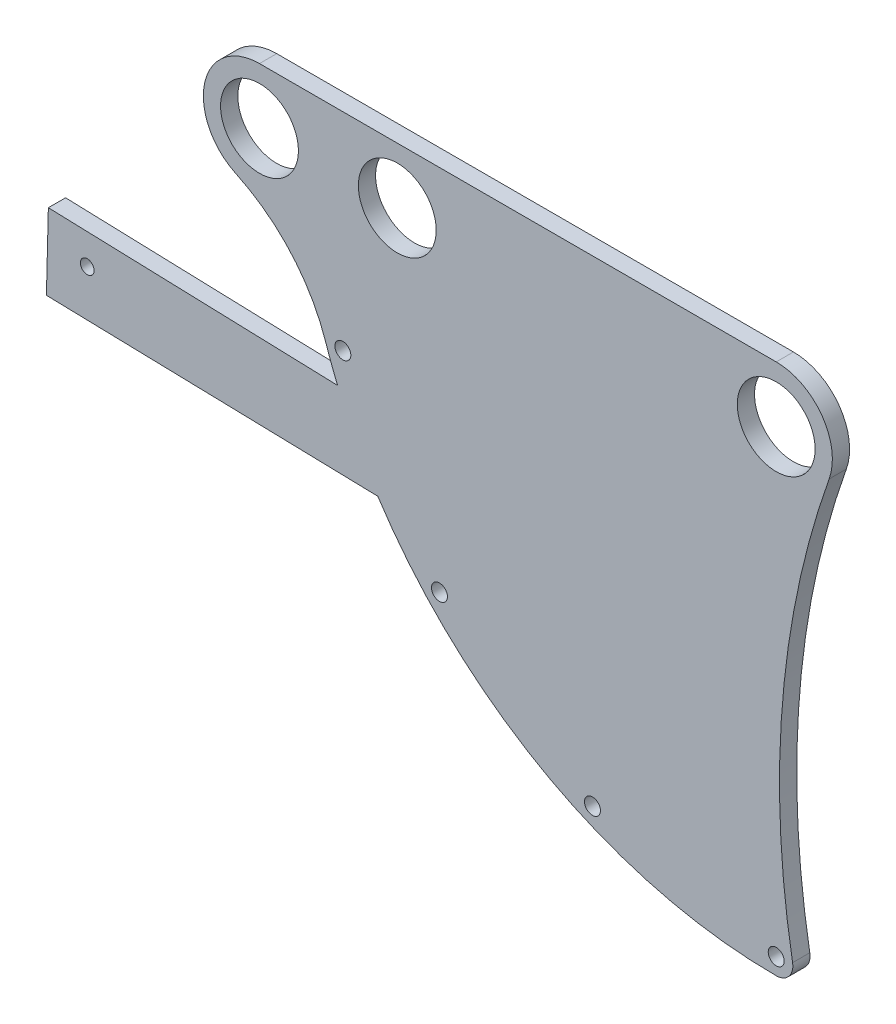
SolidWorks part; units mm, degrees
material "6061-T6 (SS)"
ref_plane "Front Plane" through (0, 0, 0) normal (0, 0, 1) x (1, 0, 0)
ref_plane "Top Plane" through (0, 0, 0) normal (0, 1, 0) x (1, 0, 0)
ref_plane "Right Plane" through (0, 0, 0) normal (1, 0, 0) x (0, 0, -1)
sketch "Sketch1" plane through (0, 0, 0) normal (0, 0, 1) x (1, 0, 0)
  line L1 (0, 0) -> (422.275, 0) construction
  line L2 (0, 0) -> (0, 250.825) construction
  line L3 (0, 250.825) -> (422.275, 250.825) construction
  line L4 (422.275, 0) -> (422.275, 250.825) construction
  line L5 (129.8504, 75.2912) -> (186.2558, 35.1899) construction
  line L6 (186.2558, 35.1899) -> (254, 21.033) construction
  line L7 (342.9, 250.825) -> (342.9, 0) construction
  line L8 (382.5875, 27.383) -> (382.5875, 190.197) construction
  line L10 (422.275, 27.383) -> (382.5875, 27.383) construction
  line L11 (0, 225.425) -> (0, 0)
  line L13 (254, 21.033) -> (129.8504, 75.2912) construction
  line L14 (250.3338, 27.383) -> (246.6677, 21.033) construction
  line L15 (246.6677, 21.033) -> (250.3338, 14.683) construction
  line L16 (250.3338, 14.683) -> (257.6662, 14.683) construction
  line L17 (257.6662, 14.683) -> (261.3323, 21.033) construction
  line L18 (261.3323, 21.033) -> (257.6662, 27.383) construction
  line L19 (257.6662, 27.383) -> (250.3338, 27.383) construction
  line L20 (185.4394, 42.4767) -> (179.5371, 38.1263) construction
  line L21 (179.5371, 38.1263) -> (180.3535, 30.8395) construction
  line L22 (180.3535, 30.8395) -> (187.0723, 27.9032) construction
  line L23 (187.0723, 27.9032) -> (192.9746, 32.2536) construction
  line L24 (192.9746, 32.2536) -> (192.1582, 39.5404) construction
  line L25 (192.1582, 39.5404) -> (185.4394, 42.4767) construction
  line L26 (132.0204, 82.2951) -> (124.8698, 80.6725) construction
  line L27 (124.8698, 80.6725) -> (122.6998, 73.6686) construction
  line L28 (122.6998, 73.6686) -> (127.6804, 68.2874) construction
  line L29 (127.6804, 68.2874) -> (134.8309, 69.91) construction
  line L30 (134.8309, 69.91) -> (137.0009, 76.9139) construction
  line L31 (137.0009, 76.9139) -> (132.0204, 82.2951) construction
  line L32 (91.186, 186.5308) -> (91.186, 193.8632) construction
  line L33 (91.186, 193.8632) -> (84.836, 197.5293) construction
  line L34 (84.836, 197.5293) -> (78.486, 193.8632) construction
  line L35 (78.486, 193.8632) -> (78.486, 186.5308) construction
  line L36 (78.486, 186.5308) -> (84.836, 182.8647) construction
  line L37 (84.836, 182.8647) -> (91.186, 186.5308) construction
  line L38 (186.2558, 35.1899) -> (94.2245, 134.6249) construction
  line L39 (186.2558, 35.1899) -> (191.9252, 48.1621) construction
  line L40 (129.8504, 75.2912) -> (140.2402, 84.9074) construction
  line L41 (129.8504, 75.2912) -> (85.3411, 203.26) construction
  line L42 (89.4313, 129.0762) -> (96.6333, 127.6995) construction
  line L43 (96.6333, 127.6995) -> (101.4265, 133.2483) construction
  line L44 (101.4265, 133.2483) -> (99.0177, 140.1737) construction
  line L45 (99.0177, 140.1737) -> (91.8158, 141.5503) construction
  line L46 (91.8158, 141.5503) -> (87.0226, 136.0016) construction
  line L47 (87.0226, 136.0016) -> (89.4313, 129.0762) construction
  line L48 (107.5958, 139.2756) -> (94.2245, 134.6249) construction
  line L49 (0, 225.425) -> (342.9, 225.425)
  line L50 (342.9, 225.425) -> (342.9, 0)
  line L51 (342.9, 0) -> (0, 0)
  line L52 (63.5, 190.197) -> (254, 190.197) construction
  circle A0 centre (254, 190.197) radius 14.351
  circle A1 centre (254, 21.033) radius 2.9464
  circle A2 centre (186.2558, 35.1899) radius 2.9464
  circle A3 centre (129.8504, 75.2912) radius 2.9464
  circle A4 centre (84.836, 190.197) radius 2.9464 construction
  arc A5 (254, 21.033) -> (84.836, 190.197) centre (254, 190.197) cw construction
  circle A10 centre (254, 190.197) radius 38.1 construction
  circle A12 centre (382.5875, 190.197) radius 38.1 construction
  circle A13 centre (254, 21.033) radius 6.35 construction
  circle A14 centre (186.2558, 35.1899) radius 6.35 construction
  circle A15 centre (129.8504, 75.2912) radius 6.35 construction
  circle A16 centre (84.836, 190.197) radius 6.35 construction
  circle A17 centre (63.5, 190.197) radius 14.351
  circle A18 centre (63.5, 190.197) radius 38.1 construction
  circle A19 centre (94.2245, 134.6249) radius 6.35 construction
  circle A20 centre (94.2245, 134.6249) radius 2.9464
  circle A21 centre (114.3, 190.197) radius 14.351
  point P21 (158.75, 190.197)
  dimension "D3" = 28.702
  dimension "D4" = 76.2
  dimension "D10" = 76.2
  dimension "D5" = 190.5
  dimension "D14" = 5.8928
  dimension "D15" = 12.7
  dimension "D18" = 50.8
  dimension "D1" = 422.275
  dimension "D2" = 225.425
  dimension "D6" = 158.75
  dimension "D7" = 162.814
  dimension "D8" = 162.814
  dimension "D9" = 223.442
  dimension "D11" = 88.9
  dimension "D12" = 39.6875
  dimension "D13" = 25.4
  dimension "D16" = 63.5
  dimension "D17" = 184.15
extrude "Boss-Extrude1" add sketch "Sketch1" along normal blind 6.35
sketch "Sketch2" plane through (0, 0, 6.35) normal (0, 0, 1) x (1, 0, 0)
  line L4 (63.5, 210.898) -> (254, 210.898)
  line L6 (349.25, 0) -> (0, 0)
  line L7 (342.9, 225.425) -> (0, 225.425) construction
  line L8 (349.25, 0) -> (349.25, 250.825)
  line L9 (0, 250.825) -> (349.25, 250.825)
  line L10 (0, 250.825) -> (0, 0)
  line L13 (349.25, 58.7375) -> (0, 58.7375) construction
  line L14 (342.9, 0) -> (342.9, 225.425) construction
  line L15 (260.0284, 22.096) -> (259.4557, 25.3442) construction
  line L16 (260.0284, 22.096) -> (260.0284, 12.3299) construction
  line L17 (349.25, 109.5375) -> (0, 109.5375) construction
  arc A0 (254, 14.9116) -> (260.0284, 22.096) centre (254, 21.033) ccw
  arc A4 (63.5, 210.898) -> (54.6994, 171.4599) centre (63.5, 190.197) ccw
  arc A5 (273.5063, 183.2663) -> (254, 210.898) centre (254, 190.197) ccw
  circle A7 centre (63.5, 190.197) radius 14.351 construction
  circle A8 centre (254, 21.033) radius 2.9464 construction
  arc A10 (273.5063, 183.2663) -> (260.0284, 22.096) centre (572.1961, 77.1396) ccw
  arc A11 (254, 14.9116) -> (87.8824, 134.2512) centre (254, 190.197) cw
  arc A12 (54.6994, 171.4599) -> (87.8824, 134.2512) centre (27.7037, 113.9839) cw
  dimension "D1" = 3.175
  dimension "D2" = 6.35
  dimension "D3" = 63.5
  dimension "D6" = 10
  dimension "D4" = 25.4
  dimension "D5" = 6.35
  dimension "D7" = 58.7375
  dimension "D8" = 50.8
sketch "Sketch3" plane through (0, 0, 6.35) normal (0, 0, 1) x (1, 0, 0)
  line L0 (63.5, 190.197) -> (254, 190.197) construction
  line L1 (0, 225.425) -> (82.55, 225.425)
  line L2 (0, 225.425) -> (0, 250.825)
  line L3 (0, 250.825) -> (82.55, 250.825)
  line L4 (82.55, 225.425) -> (82.55, 250.825)
  line L5 (342.9, 225.425) -> (234.95, 225.425)
  line L6 (342.9, 225.425) -> (342.9, 250.825)
  line L7 (342.9, 250.825) -> (234.95, 250.825)
  line L8 (234.95, 225.425) -> (234.95, 250.825)
  line L9 (82.55, 225.425) -> (234.95, 225.425) construction
  line L10 (158.75, 225.425) -> (158.75, 190.197) construction
  dimension "D1" = 25.4
  dimension "D2" = 152.4
extrude "Boss-Extrude2" add sketch "Sketch3" against normal up to surface (6.35 mm away) up to face at (171.45, 112.7125, 0)
extrude "Cut-Extrude1" cut sketch "Sketch2" against normal through all
sketch "Sketch4" plane through (0, 0, 0) normal (0, 0, -1) x (-1, 0, 0)
  line L0 (15.9711, 61.223) -> (13.8223, 146.5781) construction
  line L1 (14.3413, 125.9605) -> (-92.3008, 122.5337)
  line L2 (14.3413, 125.9605) -> (15.0546, 97.6299)
  line L3 (15.0546, 97.6299) -> (-107.1073, 94.5544)
  line L4 (0, 0) -> (0, 114.3) construction
  arc A0 (-254, 14.9116) -> (-87.8824, 134.2512) centre (-254, 190.197) ccw construction
  circle A1 centre (0, 114.3) radius 2.54
  arc A2 (-107.1073, 94.5544) -> (-92.3008, 122.5337) centre (-254, 190.197) ccw
  dimension "D2" = 5.08
  dimension "D1" = 114.3
extrude "Boss-Extrude3" add sketch "Sketch4" against normal through all contours A2 L1 L2 L3 | A1
